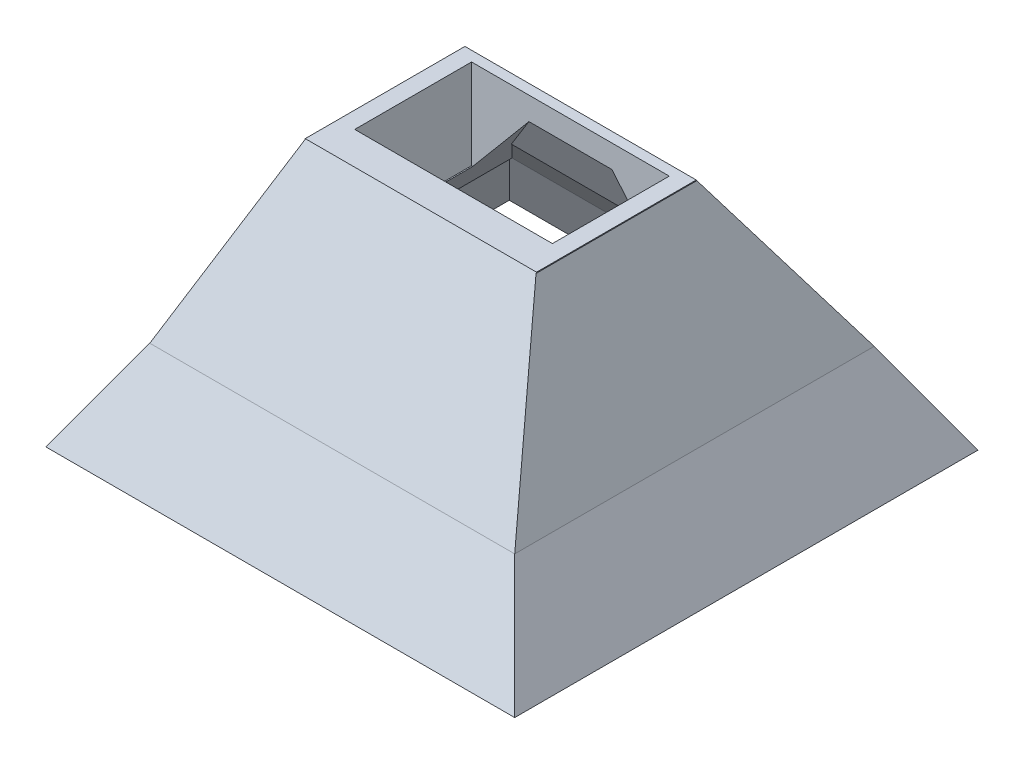
SolidWorks part; units mm, degrees
ref_plane "Front Plane" through (0, 0, 0) normal (0, 0, 1) x (1, 0, 0)
ref_plane "Top Plane" through (0, 0, 0) normal (0, 1, 0) x (1, 0, 0)
ref_plane "Right Plane" through (0, 0, 0) normal (1, 0, 0) x (0, 0, -1)
sketch "Sketch1" plane through (0, 0, 0) normal (0, 1, 0) x (1, 0, 0)
  line L1 (-20, -20) -> (20, -20)
  line L2 (-20, -20) -> (-20, 20)
  line L3 (-20, 20) -> (20, 20)
  line L4 (20, -20) -> (20, 20)
  line L5 (-20, -20) -> (20, 20) construction
  line L6 (-20, 20) -> (20, -20) construction
  point P0 (0, 0)
  dimension "D1" = 40
  dimension "D2" = 40
extrude "Boss-Extrude1" add sketch "Sketch1" along normal blind 8.5 draft 40
sketch "Sketch2" plane through (0, 0, 0) normal (0, -1, 0) x (1, 0, 0)
  line L0 (-20, 20) -> (20, 20) construction
  line L1 (-18, -18) -> (18, -18)
  line L2 (-18, -18) -> (-18, 18)
  line L3 (-18, 18) -> (18, 18)
  line L4 (18, -18) -> (18, 18)
  line L5 (-18, -18) -> (18, 18) construction
  line L6 (-18, 18) -> (18, -18) construction
  line L7 (20, 20) -> (20, -20) construction
  point P0 (0, 0)
  dimension "D1" = 2
  dimension "D2" = 2
extrude "Cut-Extrude1" cut sketch "Sketch2" against normal blind 15 draft 40
sketch "Sketch4" plane through (0, 8.5, 0) normal (0, 1, 0) x (1, 0, 0)
  line L1 (-12.8677, -12.8677) -> (12.8677, -12.8677)
  line L2 (-12.8677, -12.8677) -> (-12.8677, 12.8677)
  line L3 (-12.8677, 12.8677) -> (12.8677, 12.8677)
  line L4 (12.8677, -12.8677) -> (12.8677, 12.8677)
  line L5 (-12.8677, -12.8677) -> (12.8677, 12.8677) construction
  line L6 (-12.8677, 12.8677) -> (12.8677, -12.8677) construction
  point P1 (0, 0)
extrude "Boss-Extrude3" add sketch "Sketch4" along normal blind 10
sketch "Sketch5" plane through (0, 8.5, 0) normal (0, -1, 0) x (1, 0, 0)
  line L1 (-11, -6.5) -> (11, -6.5)
  line L2 (-11, -6.5) -> (-11, 6.5)
  line L3 (-11, 6.5) -> (11, 6.5)
  line L4 (11, -6.5) -> (11, 6.5)
  line L5 (-11, -6.5) -> (11, 6.5) construction
  line L6 (-11, 6.5) -> (11, -6.5) construction
  point P1 (0, 0)
  dimension "D1" = 22
  dimension "D2" = 13
extrude "Cut-Extrude2" cut sketch "Sketch5" against normal through all
chamfer "Chamfer2" distance 12 angle 18 4 edges at (12.8677, 8.5, 0) (-12.8677, 8.5, 0) (0, 8.5, 12.8677) (0, 8.5, -12.8677)
sketch "Sketch7" plane through (0, 0, 0) normal (1, 0, 0) x (0, 0, -1)
  line L2 (22, 0) -> (-22, 0) construction
  line L3 (-20, 0) -> (-24.7859, 0)
  line L4 (-24.7859, 0) -> (-24.7859, 18.533)
  line L7 (-10.14, 18.5) -> (-20, 0)
  line L8 (-12.8677, 18.5) -> (12.8677, 18.5) construction
  line L9 (-10.14, 18.5) -> (-24.7859, 18.533)
  dimension "D1" = 3.64
  dimension "D2" = 2
extrude "Cut-Extrude3" cut sketch "Sketch7" against normal through all both and the other way through all
chamfer "Chamfer3" distance 4.3 angle 60 2 edges at (0, 8.5, -6.5) (0, 8.5, 6.5)
sketch "Sketch8" plane through (0, 0, 0) normal (1, 0, 0) x (0, 0, -1)
  line L0 (7.63, 18.5) -> (12.8677, 18.5)
  line L1 (-10.14, 18.5) -> (12.8677, 18.5) construction
  line L2 (12.8677, 18.5) -> (21.1602, 0)
  line L3 (22.3314, 0) -> (-22.3314, 0) construction
  line L4 (21.1602, 0) -> (20, 0)
  line L5 (20, 0) -> (7.63, 18.5)
  dimension "D1" = 1.13
  dimension "D2" = 2
  dimension "D3" = 5.2377
extrude "Cut-Extrude4" cut sketch "Sketch8" against normal through all both and the other way through all
sketch "Sketch9" plane through (0, 0, 0) normal (0, -1, 0) x (1, 0, 0)
  line L1 (-20.3013, -20) -> (20.3013, -20)
  line L2 (-20.3013, -20) -> (-20.3013, 20)
  line L3 (-20.3013, 20) -> (20.3013, 20)
  line L4 (20.3013, -20) -> (20.3013, 20)
  line L5 (-20.3013, -20) -> (20.3013, 20) construction
  line L6 (-20.3013, 20) -> (20.3013, -20) construction
  point P0 (0, 0)
extrude "Boss-Extrude4" add sketch "Sketch9" along normal blind 10 draft 30 draft outward yes
sketch "Sketch10" plane through (0, 0, 0) normal (0, 1, 0) x (1, 0, 0)
  line L0 (-20.3013, 20) -> (20.3013, 20) construction
  line L1 (-18.3013, -18) -> (18.3013, -18)
  line L2 (-18.3013, -18) -> (-18.3013, 18)
  line L3 (-18.3013, 18) -> (18.3013, 18)
  line L4 (18.3013, -18) -> (18.3013, 18)
  line L5 (-18.3013, -18) -> (18.3013, 18) construction
  line L6 (-18.3013, 18) -> (18.3013, -18) construction
  line L7 (20.3013, 20) -> (20.3013, -20) construction
  point P0 (0, 0)
  dimension "D1" = 2
  dimension "D2" = 2
extrude "Cut-Extrude5" cut sketch "Sketch10" against normal blind 10 draft 30 draft outward yes
